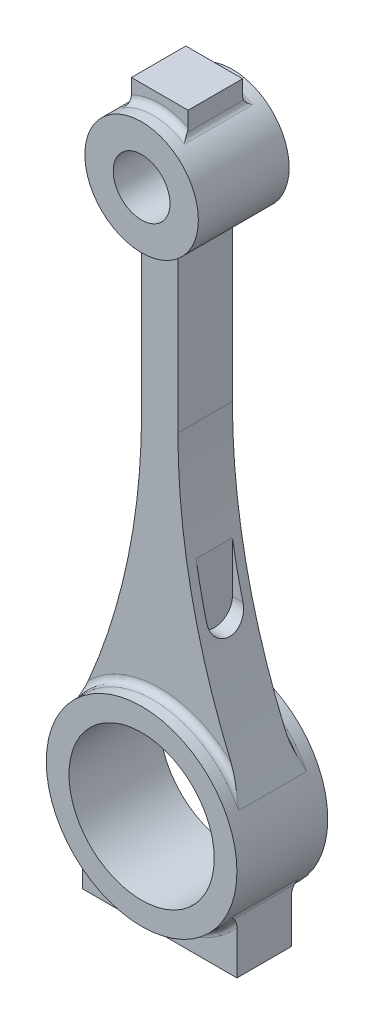
SolidWorks part; units mm, degrees
ref_plane "Front Plane" through (0, 0, 0) normal (0, 0, 1) x (1, 0, 0)
ref_plane "Top Plane" through (0, 0, 0) normal (0, 1, 0) x (1, 0, 0)
ref_plane "Right Plane" through (0, 0, 0) normal (1, 0, 0) x (0, 0, -1)
sketch "Sketch2" plane through (0, 0, 0) normal (0, 0, 1) x (1, 0, 0)
  circle A0 centre (0, 0) radius 21
  circle A1 centre (0, 0) radius 16
  circle A2 centre (0, 120) radius 12.5
  circle A3 centre (0, 120) radius 6.25
  dimension "D1" = 42
  dimension "D2" = 32
  dimension "D3" = 25
  dimension "D4" = 12.5
  dimension "D5" = 120
extrude "Boss-Extrude1" add sketch "Sketch2" along normal mid plane 20
sketch "Sketch3" plane through (0, 0, 0) normal (0, 0, 1) x (1, 0, 0)
  line L0 (4, 108.1573) -> (4, 73.1573)
  line L1 (0, 120) -> (0, 82.484) construction
  line L2 (-4, 108.1573) -> (-4, 73.1573)
  circle A0 centre (0, 0) radius 21 construction
  circle A1 centre (0, 120) radius 12.5 construction
  arc A2 (18.8482, 9.2598) -> (-18.8482, 9.2598) centre (0, 0) ccw
  arc A3 (-4, 108.1573) -> (4, 108.1573) centre (0, 120) ccw
  arc A4 (4, 73.1573) -> (18.8482, 9.2598) centre (148.9114, 73.1573) ccw
  arc A5 (-4, 73.1573) -> (-18.8482, 9.2598) centre (-148.9114, 73.1573) cw
  dimension "D1" = 8
  dimension "D2" = 35
extrude "Boss-Extrude2" add sketch "Sketch3" along normal mid plane 12
sketch "Sketch4" plane through (0, 0, 0) normal (0, 0, 1) x (1, 0, 0)
  line L0 (0, 143.1729) -> (0, -37.5594) construction
  line L1 (-6.25, 135.8253) -> (-6.25, 130.8253)
  line L2 (6.25, 135.8253) -> (6.25, 130.8253)
  line L3 (-6.25, 135.8253) -> (6.25, 135.8253)
  line L4 (-17, -24.3288) -> (-17, -12.3288)
  line L5 (17, -24.3288) -> (17, -12.3288)
  line L6 (-17, -24.3288) -> (17, -24.3288)
  circle A0 centre (0, 120) radius 12.5 construction
  arc A1 (6.25, 130.8253) -> (-6.25, 130.8253) centre (0, 120) ccw
  circle A2 centre (0, 0) radius 21 construction
  arc A3 (-17, -12.3288) -> (17, -12.3288) centre (0, 0) ccw
  dimension "D1" = 5
  dimension "D2" = 12.5
  dimension "D3" = 12
  dimension "D4" = 34
extrude "Boss-Extrude3" add sketch "Sketch4" along normal mid plane 12
fillet "Fillet1" radius 1.5 8 edges at (0, 21, -6) (0, 107.5, -6) (0, 107.5, 6) (0, 21, 6) (0, 132.5, -6) (-6.25, 130.8253, 0) (0, 132.5, 6) (6.25, 130.8253, 0)
fillet "Fillet2" radius 1.5 4 edges at (0, -21, -6) (17, -12.3288, 0) (-17, -12.3288, 0) (0, -21, 6)
ref_plane "Plane1" through (6, 0, 0) normal (1, 0, 0) x (0, 0, -1)
sketch "Sketch5" plane through (6, 0, 0) normal (1, 0, 0) x (0, 0, -1)
  line L0 (0, 100) -> (0, 38) construction
  line L1 (4, 100) -> (4, 38)
  line L2 (-4, 100) -> (-4, 38)
  line L3 (-10, 120) -> (10, 120) construction
  line L4 (-10, 132.5) -> (-10, 107.5) construction
  line L5 (10, 107.5) -> (10, 132.5) construction
  arc A0 (4, 100) -> (-4, 100) centre (0, 100) ccw
  arc A1 (-4, 38) -> (4, 38) centre (0, 38) ccw
  point P3 (0, 69)
  dimension "D1" = 4
  dimension "D2" = 62
  dimension "D3" = 20
extrude "Cut-Extrude9" cut sketch "Sketch5" along normal blind 62
mirror "Mirror3" about plane through (0, 0, 0) normal (1, 0, 0) of "Cut-Extrude9"
